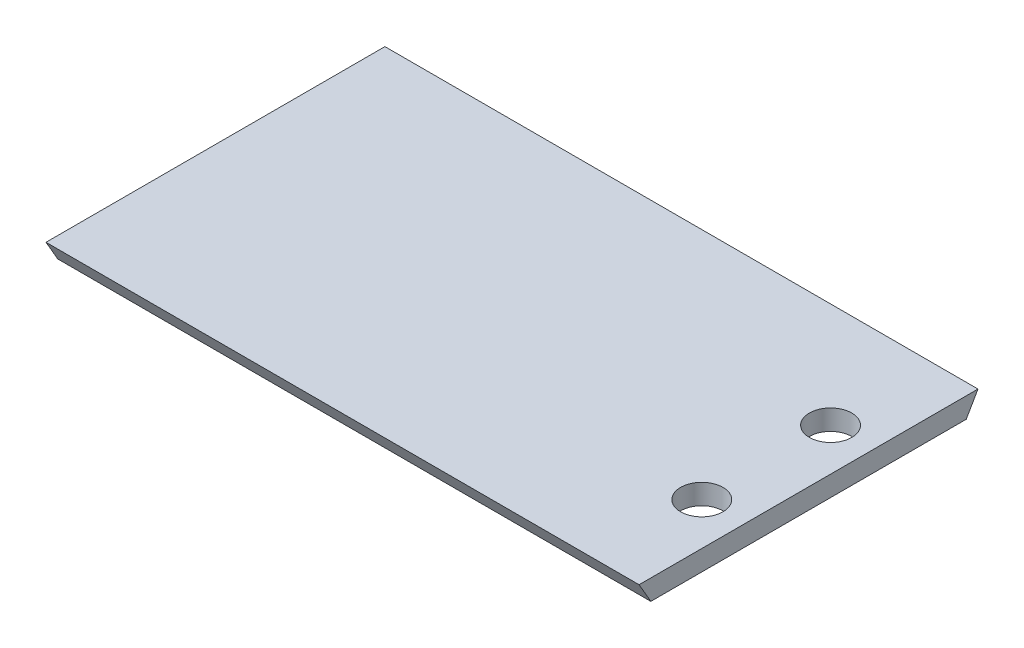
SolidWorks part; units mm, degrees
ref_plane "Front Plane" through (0, 0, 0) normal (0, 0, 1) x (1, 0, 0)
ref_plane "Top Plane" through (0, 0, 0) normal (0, 1, 0) x (1, 0, 0)
ref_plane "Right Plane" through (0, 0, 0) normal (1, 0, 0) x (0, 0, -1)
sketch "Sketch1" plane through (0, 0, 0) normal (0, 1, 0) x (1, 0, 0)
  line L0 (0, 0) -> (35, 0)
  line L1 (35, 0) -> (35, 20)
  line L2 (35, 20) -> (0, 20)
  line L3 (0, 20) -> (0, 0)
  line L4 (32.5, 0) -> (32.5, 20)
  line L8 (35, 10) -> (32.5, 10) construction
  circle A0 centre (32.5, 6.2) radius 1.25
  circle A1 centre (32.5, 13.8) radius 1.25
  dimension "D5" = 2.5
  dimension "D1" = 2.5
  dimension "D2" = 20
  dimension "D4" = 32.5
  dimension "D6" = 3.8
  dimension "D7" = 3.8
extrude "Boss-Extrude1" add sketch "Sketch1" against normal blind 1.2 contours L0 L4 L2 L3 | L8 L1 L2 L4 A1 | L1 L8 L4 A0 L0 | L0 L2 L3 | L3 region at (16.1304, 0, -10) region at (33.8283, 0, -4.8694) region at (33.8283, 0, -15.1306)
chamfer "Chamfer1" distance 1.2 angle 30 1 edges at (17.5, -1.2, -20) first distance on face at (17.5, -0.6, -20)
chamfer "Chamfer2" distance 1.2 angle 30 1 edges at (17.5, -1.2, 0) first distance on face at (17.5, -0.6, 0)
